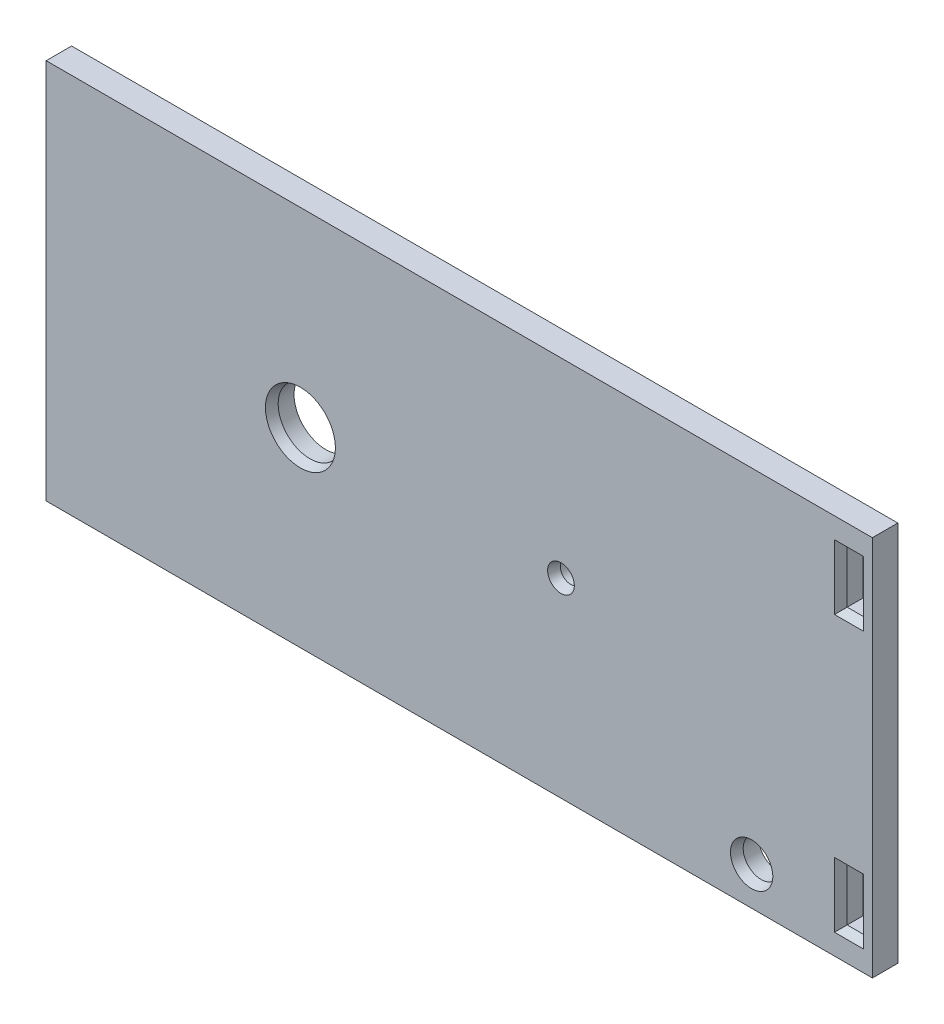
SolidWorks part; units mm, degrees
ref_plane "Front Plane" through (0, 0, 0) normal (0, 0, 1) x (1, 0, 0)
ref_plane "Top Plane" through (0, 0, 0) normal (0, 1, 0) x (1, 0, 0)
ref_plane "Right Plane" through (0, 0, 0) normal (1, 0, 0) x (0, 0, -1)
sketch "Sketch1" plane through (0, 0, 0) normal (0, 0, 1) x (1, 0, 0)
  line L2 (-65, -30) -> (-65, 30)
  line L12 (61.3, 26.25) -> (61.3, 17.05) construction
  line L13 (-65, 30) -> (65, 30)
  line L15 (-65, -30) -> (65, -30)
  line L16 (65, 30) -> (65, -30)
  line L17 (59.535, 26.25) -> (63.065, 26.25)
  line L18 (59.535, 26.25) -> (59.535, 17.05)
  line L19 (59.535, 17.05) -> (63.065, 17.05)
  line L20 (63.065, 26.25) -> (63.065, 17.05)
  line L21 (59.535, -17.05) -> (63.065, -17.05)
  line L22 (59.535, -17.05) -> (59.535, -26.25)
  line L23 (59.535, -26.25) -> (63.065, -26.25)
  line L24 (63.065, -17.05) -> (63.065, -26.25)
  line L25 (61.3, -17.05) -> (61.3, -26.25) construction
  line L26 (63.065, 21.65) -> (59.535, 21.65) construction
  line L27 (63.065, -21.65) -> (59.535, -21.65) construction
  circle A3 centre (-25, 0) radius 5
  circle A4 centre (46, -24) radius 2.83
  circle A6 centre (16, 0) radius 1.6
  point P2 (0, 30)
  point P9 (65, 0)
  dimension "D6" = 10
  dimension "D4" = 5.66
  dimension "D2" = 60
  dimension "D3" = 130
  dimension "D8" = 24
  dimension "D1" = 9.2
  dimension "D9" = 3.53
  dimension "D10" = 21.65
  dimension "D11" = 21.65
  dimension "D5" = 40
  dimension "D7" = 86.3
  dimension "D12" = 71
  dimension "D13" = 41
extrude "Boss-Extrude1" add sketch "Sketch1" along normal mid plane 4
chamfer "Chamfer1" distance 0.5 distance2 1.5 11 edges at (61.3, 17.05, 2) (59.535, 21.65, 2) (61.3, 26.25, 2) (63.065, 21.65, 2) (-20, 0, 2) (48.83, -24, 2) (61.3, -26.25, 2) (59.535, -21.65, 2) (61.3, -17.05, 2) (63.065, -21.65, 2) (17.6, 0, 2) first distance on face at (-20, 0, 2)
sketch "Sketch3" plane through (0, 0, -2) normal (0, 0, -1) x (-1, 0, 0)
  line L0 (-61.3, 26.25) -> (-61.3, 17.05) construction
  line L1 (-63.065, 21.65) -> (-59.535, 21.65) construction
  line L2 (-61.3, -17.05) -> (-61.3, -26.25) construction
  line L3 (-59.535, -17.05) -> (-63.065, -17.05) construction
  line L4 (-63.065, -21.65) -> (-59.535, -21.65) construction
equation "\"hole_width\"=3.4"
equation "\"hole_length\"=8.7"
equation "\"pin_hole_height\"=9.2"
equation "\"D1@Sketch1\"=\"pin_hole_height\""
equation "\"pin_hole_width\"=3.53"
equation "\"D9@Sketch1\"=\"pin_hole_width\""
equation "\"wall_thick_ness\"=4"
equation "\"D1@Boss-Extrude1\"=\"wall_thick_ness\""
equation "\"back_boost\"= 7"
equation "\"D5@Sketch1\"=\"back_boost\"+33.00mm"
equation "\"D3@Sketch1\"=123.00mm+\"back_boost\""
